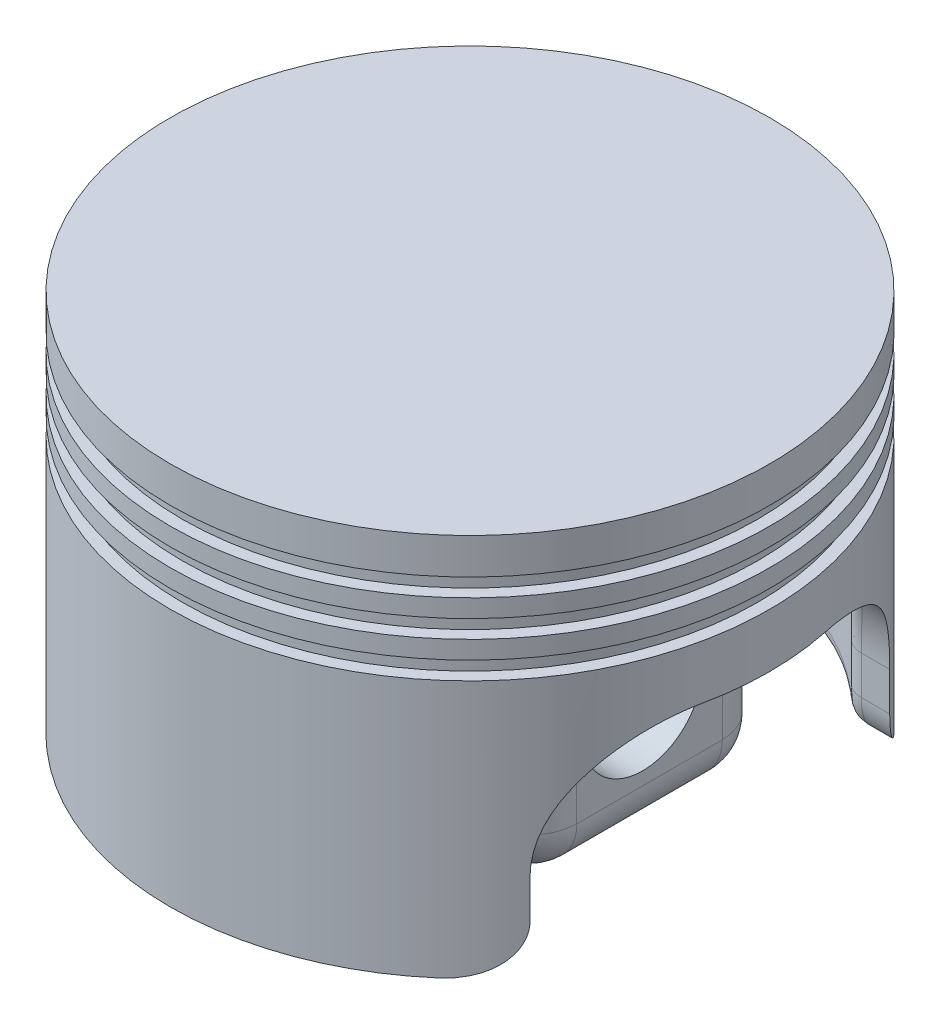
SolidWorks part; units mm, degrees
ref_plane "Front Plane" through (0, 0, 0) normal (0, 0, 1) x (1, 0, 0)
ref_plane "Top Plane" through (0, 0, 0) normal (0, 1, 0) x (1, 0, 0)
ref_plane "Right Plane" through (0, 0, 0) normal (1, 0, 0) x (0, 0, -1)
sketch "Sketch1" plane through (0, 0, 0) normal (0, 0, 1) x (1, 0, 0)
  line L0 (0, 0) -> (63.5, 0)
  line L1 (63.5, 0) -> (63.5, -81.28)
  line L2 (63.5, -81.28) -> (57.15, -81.28)
  line L3 (57.15, -81.28) -> (57.15, -19)
  line L4 (57.15, -19) -> (0, -19)
  line L5 (0, -19) -> (0, 0)
  dimension "D1" = 63.5
  dimension "D2" = 81.28
  dimension "D3" = 6.35
  dimension "D4" = 19
revolve "Revolve1" add sketch "Sketch1" angle 360 about L5
sketch "Sketch2" plane through (0, 0, 0) normal (0, 0, 1) x (1, 0, 0)
  line L0 (63.5, -7.62) -> (60.96, -7.62)
  line L1 (60.96, -7.62) -> (60.96, -11.43)
  line L2 (60.96, -11.43) -> (63.5, -11.43)
  line L3 (63.5, -11.43) -> (63.5, -7.62)
  line L4 (63.5, 0) -> (-63.5, 0) construction
  dimension "D1" = 7.62
  dimension "D2" = 3.81
  dimension "D3" = 2.54
  dimension "D4" = 63.5
ref_axis "Axis1" through (0, 0, 0) along (0, -1, 0)
revolve "Cut-Revolve1" cut sketch "Sketch2" angle 360 about axis through (0, 0, 0) along (0, -1, 0)
pattern_linear "LPattern1" count 3 spacing 7.62 along (0, -1, 0) of "Cut-Revolve1"
sketch "Sketch3" plane through (0, 0, 0) normal (1, 0, 0) x (0, 0, -1)
  line L0 (0, 0) -> (0, -81.28) construction
  line L1 (-38.1, -81.28) -> (38.1, -81.28)
  line L2 (-38.1, -81.28) -> (-38.1, -38.1)
  line L3 (-38.1, -38.1) -> (38.1, -38.1)
  line L4 (38.1, -81.28) -> (38.1, -38.1)
  line L5 (-38.1, -81.28) -> (38.1, -38.1) construction
  line L6 (-38.1, -38.1) -> (38.1, -81.28) construction
  line L7 (-57.15, -81.28) -> (57.15, -81.28) construction
  line L8 (63.5, 0) -> (-63.5, 0) construction
  point P0 (0, -59.69)
  point P7 (41.7751, -81.28)
  point P10 (0, 0)
  point P11 (43.6526, -26.4803)
  dimension "D1" = 76.2
  dimension "D2" = 38.1
extrude "Cut-Extrude1" cut sketch "Sketch3" against normal mid plane 210
fillet "Fillet1" radius 25 4 edges at (-46.6985, -38.1, -38.1) (46.6985, -38.1, -38.1) (-46.6985, -38.1, 38.1) (46.6985, -38.1, 38.1)
fillet "Fillet2" radius 10 4 edges at (-46.6985, -81.28, -38.1) (46.6985, -81.28, -38.1) (-46.6985, -81.28, 38.1) (46.6985, -81.28, 38.1)
sketch "Sketch4" plane through (0, -19, 0) normal (0, -1, 0) x (1, 0, 0)
  line L1 (-36.55, -26.8849) -> (-17.55, -26.8849)
  line L2 (-36.55, -26.8849) -> (-36.55, 23.9151)
  line L3 (-36.55, 23.9151) -> (-17.55, 23.9151)
  line L4 (-17.55, -26.8849) -> (-17.55, 23.9151)
  line L5 (-36.55, -26.8849) -> (-17.55, 23.9151) construction
  line L6 (-36.55, 23.9151) -> (-17.55, -26.8849) construction
  point P0 (-27.05, -1.4849)
  dimension "D1" = 19
  dimension "D2" = 50.8
  dimension "D3" = 17.55
extrude "Boss-Extrude1" add sketch "Sketch4" along normal blind 63.5 separate body
mirror "Mirror5" about plane through (0, 0, 0) normal (1, 0, 0) of "Boss-Extrude1"
fillet "Fillet3" radius 10 2 edges at (-27.05, -82.5, -26.8849) (-27.05, -82.5, 23.9151)
fillet "Fillet4" radius 10 2 edges at (27.05, -82.5, -26.8849) (27.05, -82.5, 23.9151)
fillet "Fillet5" radius 10 5 edges at (-36.55, -45.75, 23.9151) (-36.55, -79.5711, 20.9862) (-36.55, -45.75, -26.8849) (-36.55, -79.5711, -23.9559) (-36.55, -82.5, -1.4849)
fillet "Fillet6" radius 10 5 edges at (-17.55, -45.75, -26.8849) (-17.55, -79.5711, -23.9559) (-17.55, -45.75, 23.9151) (-17.55, -79.5711, 20.9862) (-17.55, -82.5, -1.4849)
fillet "Fillet7" radius 10 5 edges at (17.55, -45.75, -26.8849) (17.55, -79.5711, -23.9559) (17.55, -45.75, 23.9151) (17.55, -79.5711, 20.9862) (17.55, -82.5, -1.4849)
fillet "Fillet8" radius 10 5 edges at (36.55, -45.75, 23.9151) (36.55, -79.5711, 20.9862) (36.55, -45.75, -26.8849) (36.55, -79.5711, -23.9559) (36.55, -82.5, -1.4849)
sketch "Sketch5" plane through (-36.55, 0, 0) normal (-1, 0, 0) x (0, 0, 1)
  line L0 (13.9151, -82.5) -> (-16.8849, -82.5) construction
  circle A0 centre (0, -57.1) radius 12.7
  dimension "D1" = 25.4
  dimension "D2" = 25.4
extrude "Cut-Extrude2" cut sketch "Sketch5" against normal blind 156.5
fillet "Fillet10" radius 5 16 edges at (41.3657, -76.2692, 39.4335) (42.5971, -67.19, 38.1) (49.5699, -43.3611, 28.4419) (45.69, -49.8982, -34.33) (42.5971, -67.19, -38.1) (40.0022, -78.1316, -40.816) (-41.3657, -76.2692, -39.4335) (-42.5971, -67.19, -38.1) (-49.5699, -43.3611, -28.4419) (-45.69, -49.8982, 34.33) (-42.5971, -67.19, 38.1) (-40.0022, -78.1316, 40.816) (57.15, -38.1, 0) (0, -81.28, -57.15) (-57.15, -38.1, 0) (0, -81.28, 57.15)
fillet "Fillet11" radius 5 1 edges at (0, -19, -57.15)
